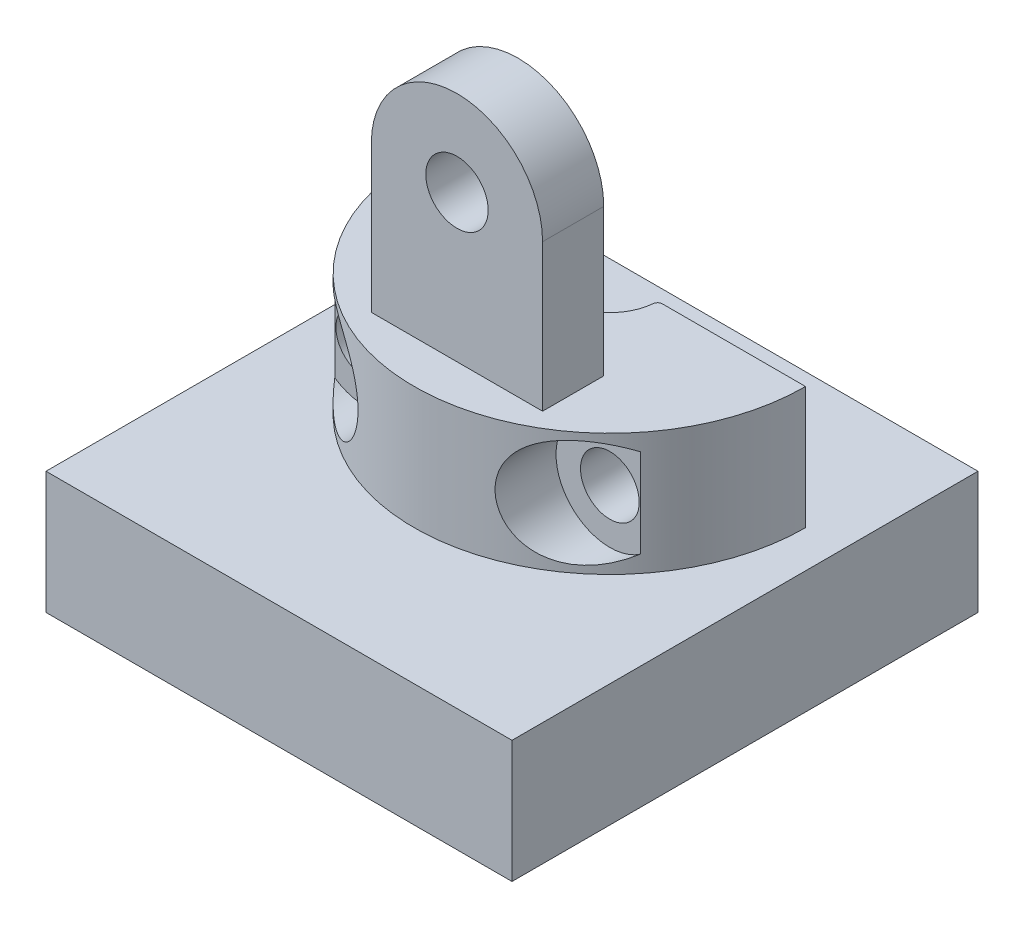
SolidWorks part; units mm, degrees
material "6061 Alloy"
ref_plane "Front Plane" through (0, 0, 0) normal (0, 0, 1) x (1, 0, 0)
ref_plane "Top Plane" through (0, 0, 0) normal (0, 1, 0) x (1, 0, 0)
ref_plane "Right Plane" through (0, 0, 0) normal (1, 0, 0) x (0, 0, -1)
sketch "Sketch1" plane through (0, 0, 0) normal (0, 1, 0) x (1, 0, 0)
  line L0 (1.96, 0) -> (8, 0)
  line L1 (-1.96, 0) -> (-8, 0)
  arc A0 (-8, 0) -> (8, 0) centre (0, 0) ccw
  arc A1 (1.96, 0) -> (-1.96, 0) centre (0, 0) cw
  dimension "D1" = 1.96
  dimension "D2" = 8
extrude "Boss-Extrude1" add sketch "Sketch1" along normal mid plane 5 contours L0 A0 L1 A1
sketch "Sketch2" plane through (0, 2.5, 0) normal (0, 1, 0) x (1, 0, 0)
  line L0 (3.5, -3.75) -> (-3.5, -3.75)
  line L1 (-3.5, -3.75) -> (-3.5, -6.25)
  line L2 (3.5, -6.25) -> (3.5, -3.75)
  line L3 (3.5, -6.25) -> (-3.5, -6.25)
  line L4 (1.96, 0) -> (8, 0) construction
  arc A0 (-1.96, 0) -> (1.96, 0) centre (0, 0) ccw construction
  dimension "D1" = 2.5
  dimension "D2" = 3.75
  dimension "D3" = 7
  dimension "D4" = 3.5
extrude "Boss-Extrude2" add sketch "Sketch2" along normal blind 9.5 contours L2 L0 L1 L3
sketch "Sketch3" plane through (0, 0, 3.75) normal (0, 0, -1) x (-1, 0, 0)
  line L0 (3.5, 12) -> (3.5, 2.5) construction
  line L1 (-3.5, 8.5) -> (-3.5, 14.8864)
  line L2 (-3.5, 14.8864) -> (0, 16.8092)
  line L3 (0, 16.8092) -> (3.5, 14.5)
  line L4 (3.5, 14.5) -> (3.5, 8.5)
  line L6 (-3.5, 12) -> (3.5, 12) construction
  line L7 (-3.5, 12) -> (-3.5, 2.5) construction
  arc A0 (3.5, 8.5) -> (-3.5, 8.5) centre (0, 8.5) ccw
extrude "Cut-Extrude1" cut sketch "Sketch3" against normal blind 9.5 contours L3 L4 A0 L1 L2
sketch "Sketch4" plane through (0, 0, 3.75) normal (0, 0, -1) x (-1, 0, 0)
  circle A0 centre (0, 8.5) radius 1.275
  dimension "D1" = 2.55
extrude "Cut-Extrude2" cut sketch "Sketch4" against normal blind 9.5
ref_plane "Plane1" through (0, 0, 7) normal (0, 0, -1) x (-1, 0, 0)
hole_wizard "CBORE for M2 SHCS1" positions "Sketch5" profile "Sketch7" counterbore size "M2" standard "ANSI Metric" end condition up to next
sketch "Sketch5" plane through (0, 0, 7) normal (0, 0, -1) x (-1, 0, 0)
  point P0 (-5, 0)
  point P2 (5, 0)
  dimension "D1" = 5
  dimension "D2" = 5
sketch "Sketch7" plane through (5, 0, 7) normal (1, 0, 0) x (0, -1, 0)
  line L0 (0, 0) -> (0, 7)
  line L1 (0, 7) -> (1.2, 7)
  line L3 (1.2, 7) -> (1.2, 2)
  line L4 (1.2, 2) -> (2.2, 2)
  line L5 (2.2, 2) -> (2.2, 0)
  line L7 (2.2, 0) -> (0, 0)
  line L11 (0, -6.35) -> (0, 107.95) construction
  dimension "Thru Hole Dia." = 2.4
  dimension "Thru Hole Depth" = 7
  dimension "C'Bore Dia." = 4.4
  dimension "C'Bore Depth" = 2
sketch "Sketch8" plane through (0, 0, 7) normal (0, 0, -1) x (-1, 0, 0)
  circle A0 centre (-5, 0) radius 2.2
  circle A1 centre (5, 0) radius 2.2
  arc A2 (-3.873, 1.8894) -> (-6.245, 1.8138) centre (-5, 0) ccw construction
  arc A3 (3.873, -1.8894) -> (6.245, -1.8138) centre (5, 0) ccw construction
extrude "Cut-Extrude3" cut sketch "Sketch8" against normal blind 9.5
sketch "Sketch9" plane through (0, 0, 0) normal (0, 0, 1) x (1, 0, 0)
  line L0 (0, 0.5) -> (-3, 2.5)
  line L1 (-1.96, 2.5) -> (-8, 2.5) construction
  line L2 (-3, 2.5) -> (0, 2.5)
  line L3 (0, 2.5) -> (0, 0.5)
  dimension "D1" = 3
  dimension "D2" = 2
sketch "Sketch10" plane through (0, 0, 0) normal (0, 0, -1) x (-1, 0, 0)
  line L0 (1.96, -2.5) -> (-1.96, -2.5)
sketch "Sketch11" plane through (0, -2.5, 0) normal (0, -1, 0) x (1, 0, 0)
  line L0 (-1.96, 0) -> (-8, 0) construction
  line L1 (9.525, 13.525) -> (-9.525, 13.525)
  line L2 (9.525, 13.525) -> (9.525, -5.525)
  line L3 (9.525, -5.525) -> (-9.525, -5.525)
  line L4 (-9.525, 13.525) -> (-9.525, -5.525)
  line L5 (9.525, 13.525) -> (-9.525, -5.525) construction
  line L6 (9.525, -5.525) -> (-9.525, 13.525) construction
  point P0 (0, 4)
  dimension "D1" = 19.05
  dimension "D2" = 19.05
  dimension "D3" = 4
extrude "Boss-Extrude3" add sketch "Sketch11" along normal blind 5
fillet "Fillet1" radius 0.2 2 edges at (-1.96, 0, 0) (1.96, 0, 0)
